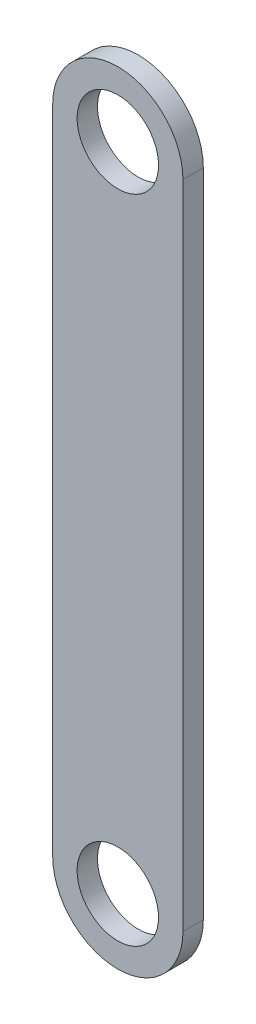
SolidWorks part; units mm, degrees
ref_plane "Front Plane" through (0, 0, 0) normal (0, 0, 1) x (1, 0, 0)
ref_plane "Top Plane" through (0, 0, 0) normal (0, 1, 0) x (1, 0, 0)
ref_plane "Right Plane" through (0, 0, 0) normal (1, 0, 0) x (0, 0, -1)
sketch "Sketch1" plane through (0, 0, 0) normal (0, 0, 1) x (1, 0, 0)
  line L0 (0, 0) -> (0, 127) construction
  line L1 (-12.7, 0) -> (-12.7, 127)
  line L2 (12.7, 0) -> (12.7, 127)
  arc A0 (-12.7, 0) -> (12.7, 0) centre (0, 0) ccw
  arc A1 (12.7, 127) -> (-12.7, 127) centre (0, 127) ccw
  circle A2 centre (0, 0) radius 7.9375
  circle A3 centre (0, 127) radius 7.9375
  point P3 (0, 63.5)
  dimension "D2" = 12.7
  dimension "D3" = 15.875
  dimension "D1" = 127
extrude "Boss-Extrude1" add sketch "Sketch1" along normal blind 3.9688
scale "Scale1" scale about centroid uniform scaling yes scale factor 0.75
